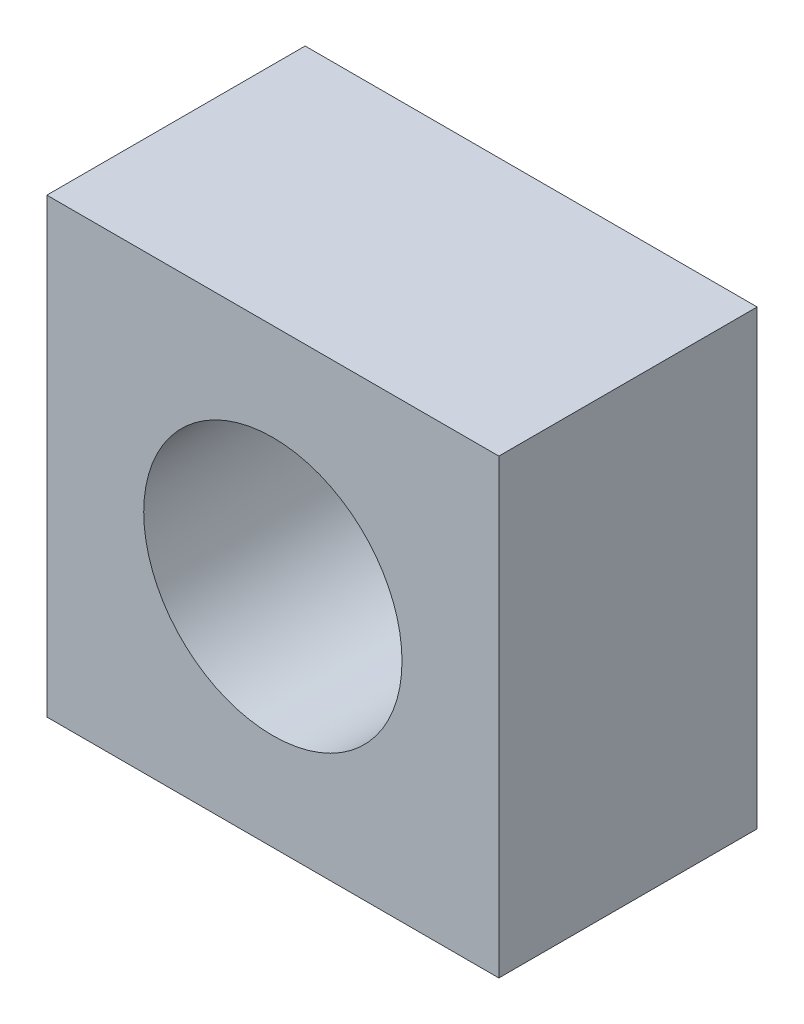
SolidWorks part; units mm, degrees
material "Tin Bearing Bronze"
ref_plane "Front Plane" through (0, 0, 0) normal (0, 0, 1) x (1, 0, 0)
ref_plane "Top Plane" through (0, 0, 0) normal (0, 1, 0) x (1, 0, 0)
ref_plane "Right Plane" through (0, 0, 0) normal (1, 0, 0) x (0, 0, -1)
sketch "Sketch1" plane through (0, 0, 0) normal (0, 0, 1) x (1, 0, 0)
  line L1 (-11.1125, -11.1125) -> (11.1125, -11.1125)
  line L2 (-11.1125, -11.1125) -> (-11.1125, 11.1125)
  line L3 (-11.1125, 11.1125) -> (11.1125, 11.1125)
  line L4 (11.1125, -11.1125) -> (11.1125, 11.1125)
  line L5 (-11.1125, -11.1125) -> (11.1125, 11.1125) construction
  line L6 (-11.1125, 11.1125) -> (11.1125, -11.1125) construction
  circle A0 centre (0, 0) radius 6.35
  point P0 (0, 0)
  dimension "D3" = 12.7
  dimension "D1" = 22.225
  dimension "D2" = 22.225
extrude "Boss-Extrude1" add sketch "Sketch1" along normal blind 12.7
ref_plane "midplane" through (0, 0, 6.35) normal (0, 0, 1) x (1, 0, 0)
ref_axis "swivel axis" through (-12.2237, 0, 6.35) along (1, 0, 0)
